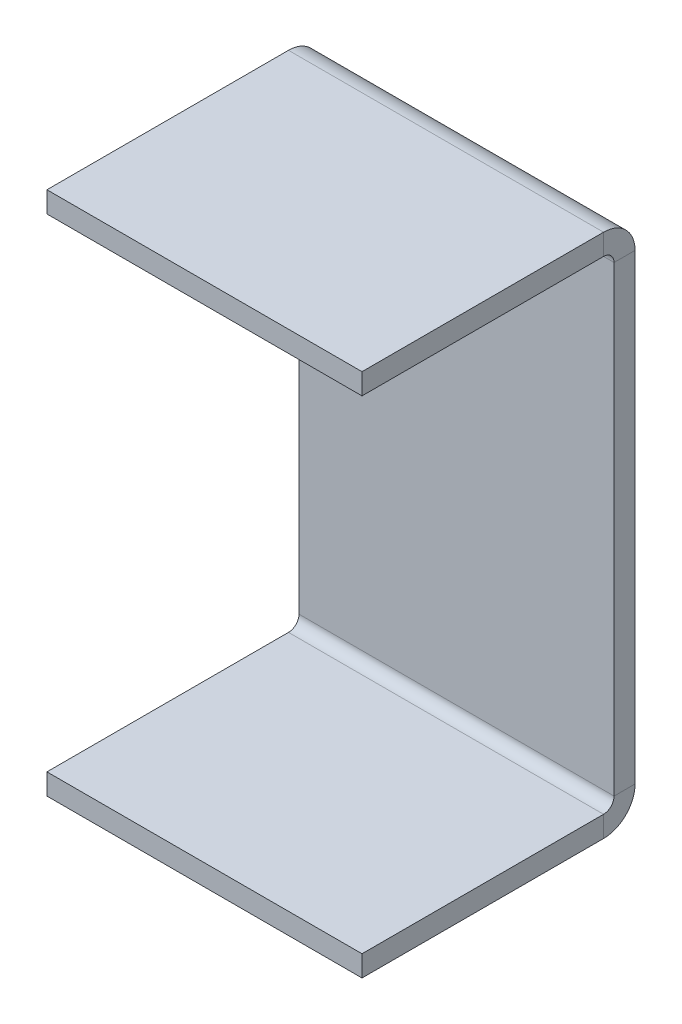
SolidWorks part; units mm, degrees
note: The reader was unsure of these and kept them because the rebuilt part matched: flange length of "边线-法兰1".
ref_plane "前视基准面" through (0, 0, 0) normal (0, 0, 1) x (1, 0, 0)
ref_plane "上视基准面" through (0, 0, 0) normal (0, 1, 0) x (1, 0, 0)
ref_plane "右视基准面" through (0, 0, 0) normal (1, 0, 0) x (0, 0, -1)
sketch "草图1" plane through (0, 0, 0) normal (0, 0, 1) x (1, 0, 0)
  line L1 (-75, 125) -> (75, 125)
  line L2 (-75, 125) -> (-75, -125)
  line L3 (-75, -125) -> (75, -125)
  line L4 (75, 125) -> (75, -125)
  line L5 (-75, 125) -> (75, -125) construction
  line L6 (-75, -125) -> (75, 125) construction
  point P0 (0, 0)
  dimension "D1" = 250
  dimension "D2" = 150
base flange "基体-法兰1" sketch "草图1" thickness 10 reverse thickness direction no parameters "D1"=1
edge flange "边线-法兰1" sketch "草图10" flange profiles "草图10", "草图11" flange angle 90 flange length 130 flange position material inside bend radius 5 thickness 10 relief rectangular parameters "D6"=10, "D8"=1
sketch "草图10" plane through (0, 125, 0) normal (0, -1, 0) x (1, 0, 0)
  line L1 (75, 0) -> (-75, 0) construction
  line L2 (-75, 0) -> (-75, 120)
  line L3 (-75, 120) -> (75, 120)
  line L4 (75, 120) -> (75, 0)
  line L5 (75, 0) -> (-75, 0)
sketch "草图11" plane through (0, -125, 0) normal (0, 1, 0) x (-1, 0, 0)
  line L0 (75, 0) -> (-75, 0) construction
  line L1 (75, 0) -> (-75, 0)
  line L2 (75, 0) -> (75, 120)
  line L3 (75, 120) -> (-75, 120)
  line L4 (-75, 120) -> (-75, 0)
bend "边线折弯1" bend radius 5 bend angle 90 parameters "D5"=1
bend "边线折弯2" bend radius 5 bend angle 90 parameters "D5"=2
sketch "折弯-线1" [suppressed] plane through (0, 0, 0) normal (0, 1, 0) x (1, 0, 0)
sketch "边界框1" [suppressed] plane through (0, 0, 0) normal (0, 1, 0) x (1, 0, 0)
sheet metal parameters "钣金6" thickness 10 parameters "D1"=1
flat pattern "平板型式6" [suppressed]
sketch "折弯-线2" plane through (0, 0, 0) normal (0, 1, 0) x (1, 0, 0)
sketch "边界框2" [suppressed] plane through (0, 0, 0) normal (0, 1, 0) x (1, 0, 0)
sheet metal parameters "钣金7" thickness 10 parameters "D1"=1
flat pattern "平板型式6"
sketch "折弯-线2" plane through (0, 0, 0) normal (0, 0, 1) x (1, 0, 0)
  line L0 (-75, -116.25) -> (75, -116.25) construction
  line L1 (75, 116.25) -> (-75, 116.25) construction
  line L2 (-75, -116.25) -> (75, -116.25) construction
  line L3 (75, 116.25) -> (-75, 116.25) construction
sketch3d "边界框2" [suppressed]
  line L0 (75, 237.5, 0) -> (75, -237.5, 0) construction
  line L1 (-75, 237.5, 0) -> (-75, -237.5, 0) construction
  line L2 (75, 237.5, 0) -> (-75, 237.5, 0) construction
  line L3 (75, -237.5, 0) -> (-75, -237.5, 0) construction
bend of the flat pattern "展开-<边线折弯1>1"
bend of the flat pattern "展开-<边线折弯2>1"
